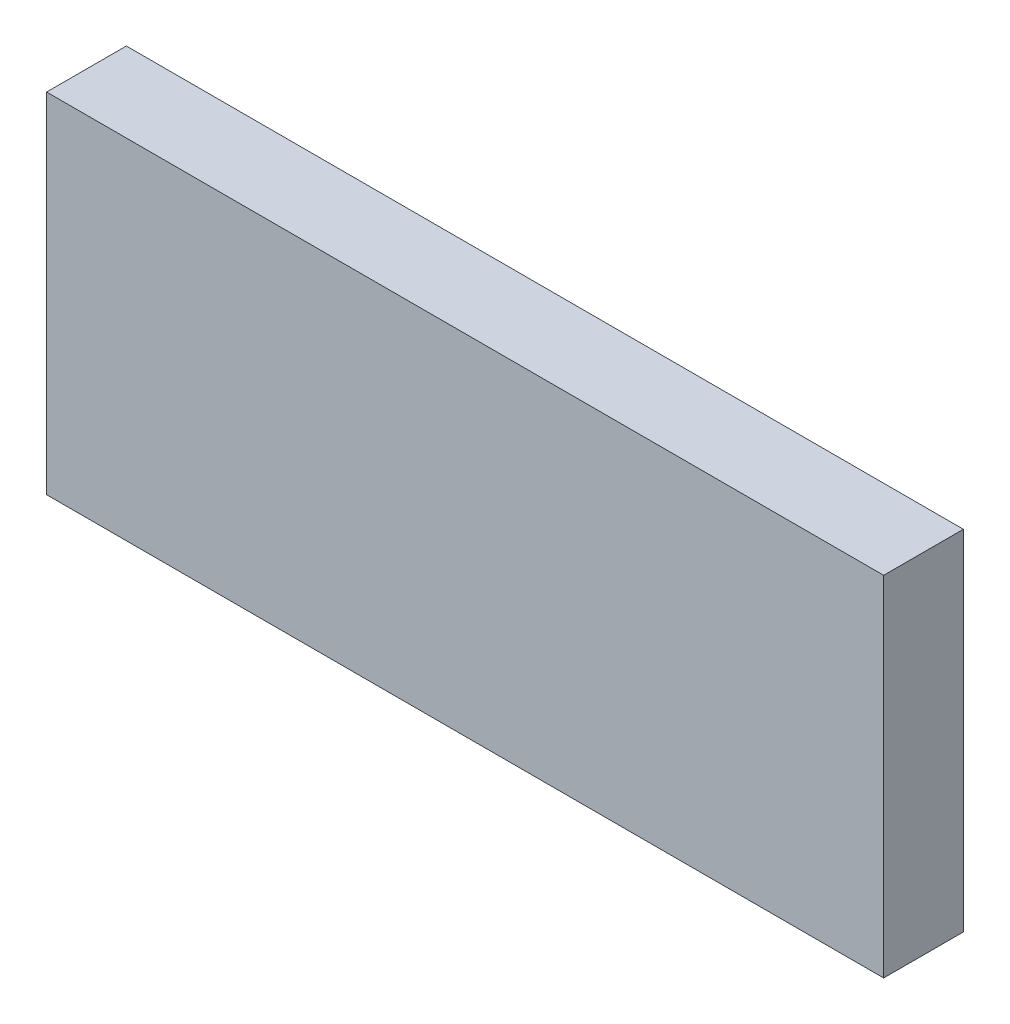
SolidWorks part; units mm, degrees
ref_plane "Front Plane" through (0, 0, 0) normal (0, 0, 1) x (1, 0, 0)
ref_plane "Top Plane" through (0, 0, 0) normal (0, 1, 0) x (1, 0, 0)
ref_plane "Right Plane" through (0, 0, 0) normal (1, 0, 0) x (0, 0, -1)
sketch "Sketch1" plane through (0, 0, 0) normal (0, 0, 1) x (1, 0, 0)
  line L1 (0, 0) -> (168, 0)
  line L2 (0, 0) -> (0, 70)
  line L3 (0, 70) -> (168, 70)
  line L4 (168, 0) -> (168, 70)
  dimension "D1" = 168
  dimension "D2" = 70
extrude "Boss-Extrude1" add sketch "Sketch1" along normal blind 16
